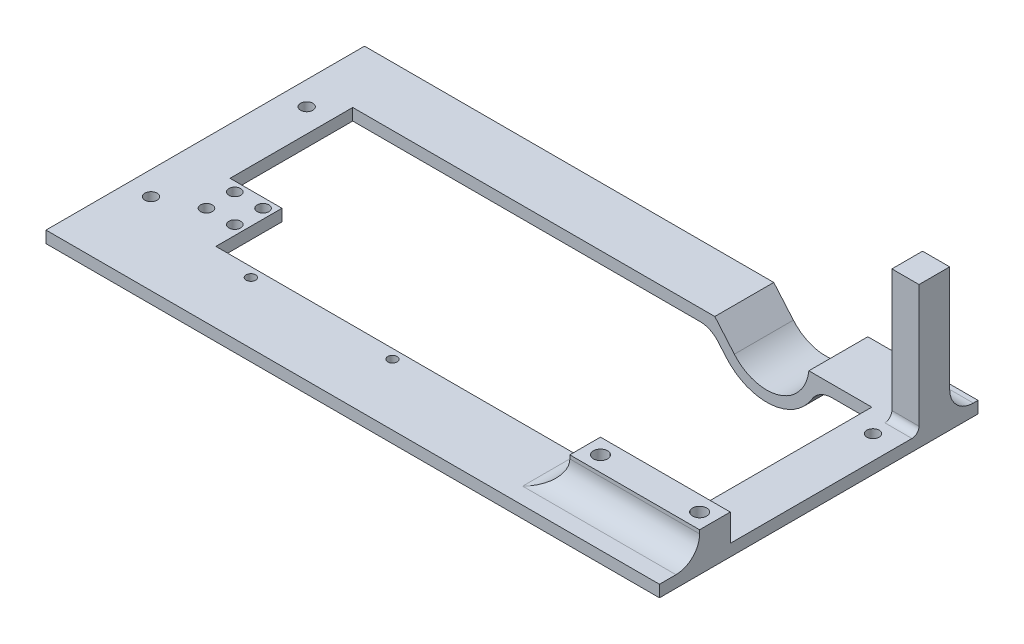
SolidWorks part; units mm, degrees
ref_plane "Front Plane" through (0, 0, 0) normal (0, 0, 1) x (1, 0, 0)
ref_plane "Top Plane" through (0, 0, 0) normal (0, 1, 0) x (1, 0, 0)
ref_plane "Right Plane" through (0, 0, 0) normal (1, 0, 0) x (0, 0, -1)
sketch "Sketch1" plane through (0, 0, 0) normal (0, 1, 0) x (1, 0, 0)
  line L35 (90, 85) -> (90, 25)
  line L36 (130, -85) -> (-130, -85)
  line L37 (130, -85) -> (130, 85)
  line L38 (130, 85) -> (-130, 85)
  line L39 (-130, -85) -> (-130, 85)
  line L40 (130, -85) -> (-130, 85) construction
  line L41 (130, 85) -> (-130, -85) construction
  line L42 (90, 25) -> (110, 25)
  line L43 (110, 25) -> (110, -55)
  line L44 (110, -55) -> (80, -55)
  line L45 (80, -55) -> (80, -85)
  line L46 (80, -55) -> (-88, -55)
  line L47 (-110, -27) -> (-110, 85)
  line L48 (-110, -27) -> (-88, -27)
  line L49 (-88, -27) -> (-88, -85)
  point P0 (0, 0)
  dimension "D1" = 170
  dimension "D2" = 260
  dimension "D3" = 30
  dimension "D4" = 80
  dimension "D5" = 40
  dimension "D6" = 50
  dimension "D7" = 20
  dimension "D8" = 190
  dimension "D9" = 42
  dimension "D10" = 58
extrude "Boss-Extrude1" add sketch "Sketch1" along normal blind 5 contours L44 L45 L36 L37 L38 L35 L42 L43 | L46 L47 L38 L39 L36 L45 | L46 L49 L36 L45 region at (111.5455, 0, -0.5455) region at (-114.2695, 0, 15.2814) region at (-4, 0, 70)
sketch "Sketch2" plane through (0, 5, 0) normal (0, 1, 0) x (1, 0, 0)
  line L0 (130, -85) -> (-130, -85) construction
  line L5 (75, -55) -> (130, -55)
  line L6 (75, -55) -> (75, -68)
  line L7 (75, -68) -> (130, -68)
  line L8 (130, -55) -> (130, -68)
  line L9 (75, -55) -> (130, -68) construction
  line L10 (75, -68) -> (130, -55) construction
  line L11 (130, -85) -> (130, 85) construction
  line L12 (75, -61.5) -> (130, -61.5) construction
  circle A0 centre (81.5, -61.5) radius 3
  circle A1 centre (123.5, -61.5) radius 3
  point P0 (102.5, -61.5)
  dimension "D7" = 6
  dimension "D1" = 23.5
  dimension "D2" = 6.5
  dimension "D3" = 55
  dimension "D4" = 27.5
  dimension "D5" = 42
  dimension "D6" = 21
extrude "Boss-Extrude2" add sketch "Sketch2" along normal blind 11.5
sketch "Sketch3" plane through (0, 5, 0) normal (0, 1, 0) x (1, 0, 0)
  line L0 (130, -85) -> (-130, -85) construction
  line L1 (118.5, 38) -> (130, 38)
  line L2 (118.5, 38) -> (118.5, 25)
  line L3 (118.5, 25) -> (130, 25)
  line L4 (130, 38) -> (130, 25)
  line L5 (118.5, 38) -> (130, 25) construction
  line L6 (118.5, 25) -> (130, 38) construction
  line L8 (130, -55) -> (130, 85) construction
  point P0 (124.25, 31.5)
  dimension "D1" = 116.5
  dimension "D2" = 13
  dimension "D3" = 11.5
extrude "Boss-Extrude3" add sketch "Sketch3" along normal blind 55
sketch "Sketch4" plane through (0, 0, -85) normal (0, 0, -1) x (-1, 0, 0)
  line L0 (-90, 5) -> (-83.3085, 5)
  line L1 (-90, 0) -> (-86.8034, 0)
  line L3 (-43.4493, 5) -> (110, 5)
  line L4 (-41.8034, 0) -> (110, 0)
  line L7 (-130, 5) -> (-90, 5)
  line L8 (-130, 5) -> (-130, 0)
  line L9 (-130, 0) -> (-90, 0)
  line L10 (110, 5) -> (130, 5)
  line L11 (130, 5) -> (130, 0)
  line L12 (130, 0) -> (110, 0)
  line L13 (-51.7378, -4.696) -> (-43.4493, 5)
  line L14 (-41.8034, 0) -> (-48.3172, -7.62)
  arc A0 (-83.3085, 5) -> (-51.7378, -4.696) centre (-65.42, 7) ccw
  arc A1 (-86.8034, 0) -> (-48.3172, -7.62) centre (-65.42, 7) ccw
  circle A2 centre (-65.42, 7) radius 18 construction
  circle A3 centre (-65.42, 7) radius 22.5 construction
  dimension "D1" = 45
  dimension "D2" = 36
  dimension "D3" = 2
  dimension "D4" = 64.58
  dimension "D5" = 45
extrude "Boss-Extrude4" add sketch "Sketch4" against normal blind 60
sketch "Sketch5" plane through (0, 0, -85) normal (0, 0, -1) x (-1, 0, 0)
  line L0 (130, 5) -> (130, 0) construction
  line L1 (-130, 5) -> (-130, 0) construction
  line L2 (-43.4493, 5) -> (130, 5) construction
  line L3 (-41.8034, 0) -> (130, 0) construction
  line L4 (-48.3172, -7.62) -> (-41.8034, 0) construction
  line L5 (-43.4493, 5) -> (-51.7378, -4.696) construction
  line L6 (-130, 0) -> (-86.8034, 0) construction
  line L7 (-130, 5) -> (-83.3085, 5) construction
  line L8 (130, 5) -> (130, 0)
  line L9 (-130, 5) -> (-130, 0)
  line L10 (-43.4493, 5) -> (130, 5)
  line L11 (-41.8034, 0) -> (130, 0)
  line L12 (-48.3172, -7.62) -> (-41.8034, 0)
  line L13 (-43.4493, 5) -> (-51.7378, -4.696)
  line L14 (-130, 0) -> (-86.8034, 0)
  line L15 (-130, 5) -> (-83.3085, 5)
  arc A0 (-83.3085, 5) -> (-51.7378, -4.696) centre (-65.42, 7) ccw construction
  arc A1 (-86.8034, 0) -> (-48.3172, -7.62) centre (-65.42, 7) ccw construction
  arc A2 (-83.3085, 5) -> (-51.7378, -4.696) centre (-65.42, 7) ccw
  arc A3 (-86.8034, 0) -> (-48.3172, -7.62) centre (-65.42, 7) ccw
extrude "Cut-Extrude1" cut sketch "Sketch5" against normal blind 35
sketch "Sketch6" plane through (0, 5, 0) normal (0, 1, 0) x (1, 0, 0)
  line L0 (-110, -27) -> (-88, -27) construction
  line L1 (-88, -27) -> (-88, -47) construction
  line L2 (-88, -27) -> (-88, -55) construction
  line L3 (-88, -47) -> (-108, -47) construction
  line L5 (-108, -37) -> (-88, -37) construction
  line L6 (-130, -59) -> (-9.17, -59) construction
  line L7 (-130, -85) -> (-130, 50) construction
  line L8 (75, -55) -> (-88, -55) construction
  line L9 (-108, -27) -> (-108, -47) construction
  circle A0 centre (-104, -31) radius 2.5
  circle A1 centre (-92, -31) radius 2.5
  circle A2 centre (-92, -43) radius 2.5
  circle A3 centre (-104, -43) radius 2.5
  circle A4 centre (-9.17, -59) radius 2
  circle A5 centre (-69.17, -59) radius 2
  dimension "D4" = 5
  dimension "D9" = 4
  dimension "D1" = 20
  dimension "D2" = 20
  dimension "D3" = 4
  dimension "D5" = 4
  dimension "D6" = 60.83
  dimension "D7" = 60
  dimension "D8" = 4
  dimension "D10" = 4
extrude "Cut-Extrude2" cut sketch "Sketch6" against normal blind 10
sketch "Sketch7" plane through (0, 5, 0) normal (0, 1, 0) x (1, 0, 0)
  line L0 (-130, 50) -> (130, -85) construction
  line L1 (0, -17.5) -> (0, 50) construction
  line L2 (-130, 50) -> (43.4493, 50) construction
  line L3 (120, 50) -> (120, -85) construction
  line L4 (83.3085, 50) -> (130, 50) construction
  line L5 (130, -85) -> (-130, -85) construction
  line L6 (118.5, 25) -> (130, 25) construction
  line L7 (130, -55) -> (130, 25) construction
  line L8 (130, -55) -> (110, -55) construction
  circle A0 centre (120, 15.5) radius 2.6
  circle A1 centre (120, -50.5) radius 2.6
  circle A2 centre (-120, -50.5) radius 2.6
  circle A3 centre (-120, 15.5) radius 2.6
  dimension "D1" = 5.2
  dimension "D2" = 9.5
  dimension "D3" = 10
  dimension "D4" = 4.5
extrude "Cut-Extrude3" cut sketch "Sketch7" against normal blind 10
sketch "Sketch8" plane through (118.5, 0, 0) normal (-1, 0, 0) x (0, 0, 1)
  line L0 (-38, 32.5) -> (-25, 32.5) construction
  line L1 (-38, 60) -> (-38, 5) construction
  line L2 (-25, 60) -> (-25, 5) construction
  line L3 (-31.5, 60) -> (-31.5, 5) construction
  line L4 (-38, 60) -> (-25, 60) construction
  line L5 (-38, 5) -> (-25, 5) construction
  circle A0 centre (-31.5, 53.5) radius 3
  circle A1 centre (-31.5, 11.5) radius 3
  point P18 (-48.897, 30.7485)
  dimension "D1" = 6
  dimension "D2" = 6
  dimension "D3" = 42
  dimension "D4" = 21
extrude "Cut-Extrude4" cut sketch "Sketch8" against normal blind 6
fillet "Fillet1" radius 10 3 edges at (124.25, 5, -38) (75, 5, 61.5) (102.5, 5, 68)
fillet "Fillet2" radius 3 1 edges at (124.25, 5, -25)
fillet "Fillet3" radius 10 2 edges at (41.8034, 0, -37.5) (86.8034, 0, -37.5)
